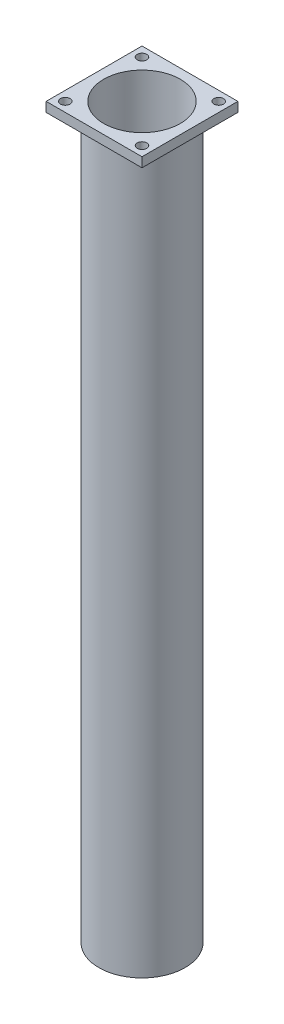
SolidWorks part; units mm, degrees
ref_plane "Alzado" through (0, 0, 0) normal (0, 0, 1) x (1, 0, 0)
ref_plane "Planta" through (0, 0, 0) normal (0, 1, 0) x (1, 0, 0)
ref_plane "Vista lateral" through (0, 0, 0) normal (1, 0, 0) x (0, 0, -1)
sketch "Croquis1" plane through (0, 0, 0) normal (0, 1, 0) x (1, 0, 0)
  line L0 (-10.3175, 0) -> (10.4762, 0) construction
  line L1 (-25, -25) -> (25, -25)
  line L2 (-25, -25) -> (-25, 25)
  line L3 (-25, 25) -> (25, 25)
  line L4 (25, -25) -> (25, 25)
  line L5 (-25, -25) -> (25, 25) construction
  line L6 (-25, 25) -> (25, -25) construction
  line L7 (0, 16.0883) -> (0, -11.0299) construction
  circle A0 centre (0, 0) radius 22.5
  circle A1 centre (-20, 20) radius 2.5
  circle A2 centre (-20, -20) radius 2.5
  circle A3 centre (20, -20) radius 2.5
  circle A4 centre (20, 20) radius 2.5
  point P0 (0, 0)
  dimension "D3" = 45
  dimension "D4" = 5
  dimension "D1" = 50
  dimension "D2" = 50
  dimension "D5" = 5
extrude "Saliente-Extruir1" add sketch "Croquis1" along normal blind 5
sketch "Croquis2" plane through (0, 0, 0) normal (0, -1, 0) x (1, 0, 0)
  circle A0 centre (0, 0) radius 22.5
extrude "Saliente-Extruir2" add sketch "Croquis2" along normal blind 375 separate body
sketch "Croquis4" plane through (0, -375, 0) normal (0, -1, 0) x (1, 0, 0)
  circle A0 centre (0, 0) radius 20
  dimension "D1" = 40
extrude "Cortar-Extruir1" cut sketch "Croquis4" against normal blind 375
thread "Rosca1" pitch 1.5875 method cut profile "Perfil de rosca1" start angle 0, offset 0, length 20, pitch 1.5875, diameter 40
ref_plane "Plano1" through (20, -375, 0) normal (0, 0, 1) x (1, 0, 0)
sketch "Perfil de rosca1" plane through (20, -375, 0) normal (0, 0, 1) x (1, 0, 0)
  line L0 (0, 0) -> (0, 1.5875) construction
  line L1 (0, 0) -> (0.8593, 0.4961)
  line L2 (0.8593, 0.4961) -> (0.8593, 0.6945)
  line L3 (0.8593, 0.6945) -> (0, 1.1906)
  line L4 (0.8593, 0.5953) -> (0, 0.5953) construction
  line L11 (0, 0) -> (0, 1.1906)
  point P2 (0, 0)
  dimension "Pitch" = 1.5875
  dimension "Profile_Angle" = 60
  dimension "Profile_Land" = 0.1984
  dimension "Profile_Height" = 0.8593
sketch "Croquis5" plane through (0, 0, 0) normal (0, 1, 0) x (1, 0, 0)
  circle A0 centre (0, 0) radius 22.5
  circle A1 centre (0, 0) radius 20
  dimension "D1" = 45
  dimension "D2" = 40
extrude "Saliente-Extruir3" add sketch "Croquis5" along normal up to surface (5 mm away) up to face at (0, 5, 0)
fillet "Redondeo2" radius 2 1 edges at (0, 0, -22.5)
